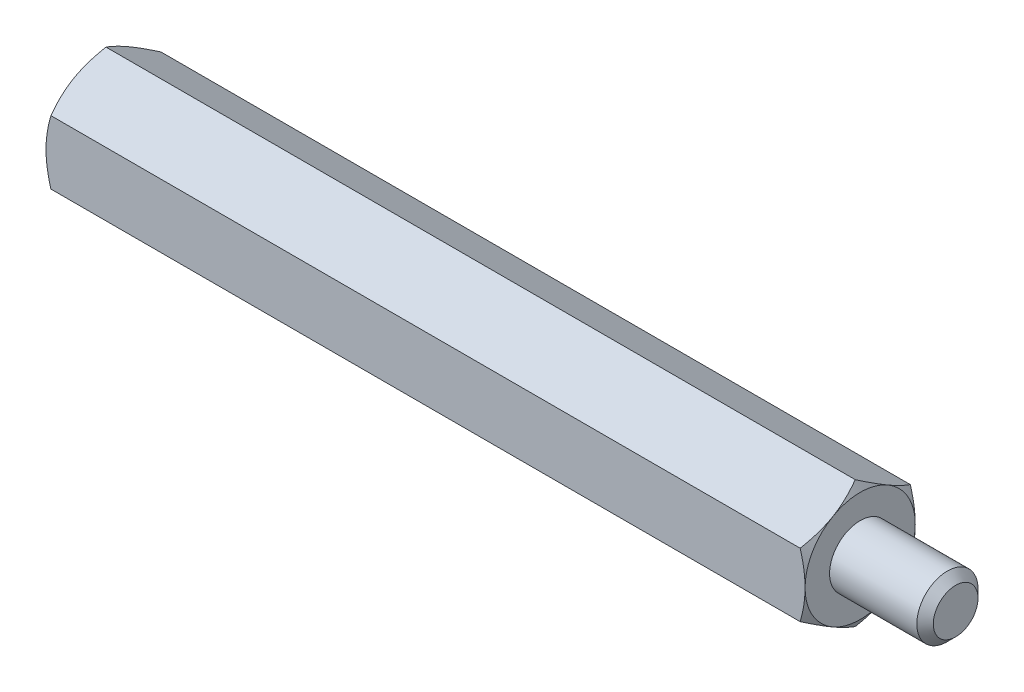
SolidWorks part; units mm, degrees
ref_plane "Front Plane" through (0, 0, 0) normal (0, 0, 1) x (1, 0, 0)
ref_plane "Top Plane" through (0, 0, 0) normal (0, 1, 0) x (1, 0, 0)
ref_plane "Right Plane" through (0, 0, 0) normal (1, 0, 0) x (0, 0, -1)
sketch "Sketch1" plane through (0, 0, 0) normal (0, 0, 1) x (1, 0, 0)
  line L0 (-17.45, 0) -> (17.45, 0) construction
  line L1 (17.45, 1.25) -> (17.45, -1.25) construction
  line L2 (-17.45, 2.25) -> (-17.45, -2.25) construction
  line L3 (-12.65, 1.25) -> (-12.65, -1.25) construction
  line L4 (-12.65, -1.25) -> (-17.45, -1.25) construction
  line L5 (-12.65, 1.25) -> (-17.45, 1.25) construction
  line L6 (-17.45, 2.25) -> (13.55, 2.25) construction
  line L7 (-17.45, -2.25) -> (13.55, -2.25) construction
  point P2 (13.55, 0)
  point P8 (-12.65, 0)
  point P13 (15.425, -1.25)
  dimension "Hex" = 4.5
  dimension "Male Thread" = 2.5
  dimension "A" = 31
  dimension "B" = 3.9
  dimension "C" = 4.8
  dimension "Female Thread" = 2.5
  dimension "D1" = 2.025
ref_plane "Plane1" through (17.45, 0, 0) normal (1, 0, 0) x (0, 0, -1)
sketch "Sketch2" plane through (17.45, 0, 0) normal (1, 0, 0) x (0, 0, -1)
  circle A0 centre (0, 0) radius 1.25
extrude "Extrude1" add sketch "Sketch2" against normal up to vertex (3.9 mm away) up to point (13.55, 0, 0)
sketch "Sketch3" plane through (17.45, 0, 0) normal (1, 0, 0) x (0, 0, -1)
  circle A1 centre (0, 0) radius 1.25
  circle A2 centre (0, 0) radius 1.25
  dimension "D1" = 0
curve "Helix/Spiral1" [suppressed] pitch 0.45 height 4.35 turns 9.6667 parameters "Male Pitch"=0.45
chamfer "Chamfer1" distance 0.3375 angle 45 1 edges at (17.45, 0, -1.25)
sketch "Sketch4" plane through (0, 0, 0) normal (0, 0, 1) x (1, 0, 0)
  line L0 (17.45, 1.25) -> (17.8438, 1.25)
  line L1 (17.8438, 1.25) -> (17.675, 0.9577)
  line L2 (17.675, 0.9577) -> (17.6188, 0.9577)
  line L3 (17.6188, 0.9577) -> (17.45, 1.25)
  line L4 (17.6469, 0.9577) -> (17.6469, 1.25) construction
  line L5 (17.5344, 1.1039) -> (17.7594, 1.1039) construction
  dimension "D1" = 0.0563
  dimension "D2" = 0.225
  dimension "D3" = 60
sweep "Cut-Sweep1" [suppressed] cut profiles "Sketch4" path "Helix/Spiral1"
sketch "Sketch16" [suppressed] plane through (0, 0, 0) normal (0, 0, 1) x (1, 0, 0)
  line L0 (13.55, 0.9552) -> (14.3375, 0.9552)
  line L1 (14.3375, 0.9552) -> (14.6323, 1.25)
  line L2 (14.6323, 1.25) -> (13.55, 1.25)
  line L3 (13.55, 1.25) -> (13.55, 0.9552)
  line L4 (17.45, 1.25) -> (17.8438, 1.25) construction
  line L5 (0, 0) -> (17.45, 0) construction
  line L6 (17.45, -0.9125) -> (17.45, 0.9125) construction
  dimension "D1" = 0.7875
  dimension "D2" = 45
  dimension "D3" = 0.0025
revolve "Cut-Revolve1" [suppressed] cut sketch "Sketch16" angle 360 about L5
ref_plane "Plane2" through (13.55, 0, 0) normal (1, 0, 0) x (0, 0, -1)
sketch "Sketch7" plane through (13.55, 0, 0) normal (1, 0, 0) x (0, 0, -1)
  line L1 (0, 2.5981) -> (-2.25, 1.299)
  line L2 (-2.25, 1.299) -> (-2.25, -1.299)
  line L3 (-2.25, -1.299) -> (0, -2.5981)
  line L4 (0, -2.5981) -> (2.25, -1.299)
  line L5 (2.25, -1.299) -> (2.25, 1.299)
  line L6 (2.25, 1.299) -> (0, 2.5981)
  circle A0 centre (0, 0) radius 2.25 construction
extrude "Extrude4" add sketch "Sketch7" against normal up to vertex (31 mm away) up to point (-17.45, 0, 0)
sketch "Sketch17" plane through (0, 0, 0) normal (0, 0, 1) x (1, 0, 0)
  line L0 (-17.45, -2.5981) -> (13.55, -2.5981) construction
  line L1 (-17.45, 2.5981) -> (13.55, 2.5981) construction
  line L2 (-17.45, -2.5981) -> (13.55, -2.5981)
  line L3 (-17.45, 2.5981) -> (13.55, 2.5981)
sketch "Sketch8" plane through (-17.45, 0, 0) normal (-1, 0, 0) x (0, 0, 1)
  circle A0 centre (0, 0) radius 2.25 construction
  circle A1 centre (0, 0) radius 2.25
extrude "Extrude5" cut sketch "Sketch8" against normal through all draft 60 flip side to cut
sketch "Sketch9" plane through (13.55, 0, 0) normal (1, 0, 0) x (0, 0, -1)
  circle A0 centre (0, 0) radius 2.25 construction
  circle A1 centre (0, 0) radius 2.25
extrude "Extrude6" cut sketch "Sketch9" against normal through all draft 60 flip side to cut
sketch "Sketch10" plane through (-17.45, 0, 0) normal (-1, 0, 0) x (0, 0, 1)
  line L0 (0, 0) -> (-0.8839, 0.8839) construction
  line L1 (0, 0) -> (-1.25, 0) construction
  circle A0 centre (0, 0) radius 1.25
  dimension "D1" = 45
extrude "Extrude7" cut sketch "Sketch10" against normal up to vertex (4.8 mm away) up to point (-12.65, 0, 0)
sketch "Sketch11" plane through (-17.45, 0, 0) normal (-1, 0, 0) x (0, 0, 1)
  circle A0 centre (0, 0) radius 1.25 construction
  circle A1 centre (0, 0) radius 1.25
curve "Helix/Spiral2" [suppressed] pitch 0.45 height 4.8 turns 10.6667 parameters "Female Pitch"=0.45
sketch "Sketch12" plane through (0, 0, 0) normal (0, 0, 1) x (1, 0, 0)
  line L0 (-17.8438, 1.25) -> (-17.675, 0.9577)
  line L1 (-17.675, 0.9577) -> (-17.6187, 0.9577)
  line L2 (-17.6187, 0.9577) -> (-17.45, 1.25)
  line L3 (-17.8438, 1.25) -> (-17.45, 1.25)
  line L4 (-17.6469, 0.9577) -> (-17.6469, 1.25) construction
  line L5 (-17.45, 2.25) -> (-17.45, -2.25) construction
  line L6 (-17.7594, 1.1039) -> (-17.5344, 1.1039) construction
  dimension "D1" = 60
  dimension "D2" = 0.0563
  dimension "D3" = 0.225
sweep "Sweep3" [suppressed] add profiles "Sketch12" path "Helix/Spiral2"
sketch "Sketch13" plane through (-17.45, 0, 0) normal (-1, 0, 0) x (0, 0, 1)
  circle A2 centre (0, 0) radius 1.3008
  circle A3 centre (0, 0) radius 1.3008
  dimension "D1" = 0.0508
extrude "Extrude8" cut sketch "Sketch13" along normal through all and the other way through all draft 45
equation "\"D3@Helix/Spiral1\" = \"B@Sketch1\"+\"Male Pitch@Helix/Spiral1\"*1"
equation "\"D1@Chamfer1\" = \"Male Pitch@Helix/Spiral1\"*.750"
equation "\"D1@Sketch4\" = \"Male Pitch@Helix/Spiral1\"*.125"
equation "\"D2@Sketch4\" = \"Male Pitch@Helix/Spiral1\"*.5"
equation "\"D2@Sketch12\" = \"Male Pitch@Helix/Spiral1\"*.125"
equation "\"D3@Sketch12\" = \"Male Pitch@Helix/Spiral1\"*.5"
equation "\"D3@Helix/Spiral2\" = \"C@Sketch1\""
equation "\"Female Thread@Sketch1\" = \"Male Thread@Sketch1\""
equation "\"Female Pitch@Helix/Spiral2\" = \"Male Pitch@Helix/Spiral1\""
equation "\"D1@Sketch16\" = \"Male Pitch@Helix/Spiral1\"*1.75"
equation "\"D1@Sketch1\" = \"Male Pitch@Helix/Spiral1\"*4.5"
